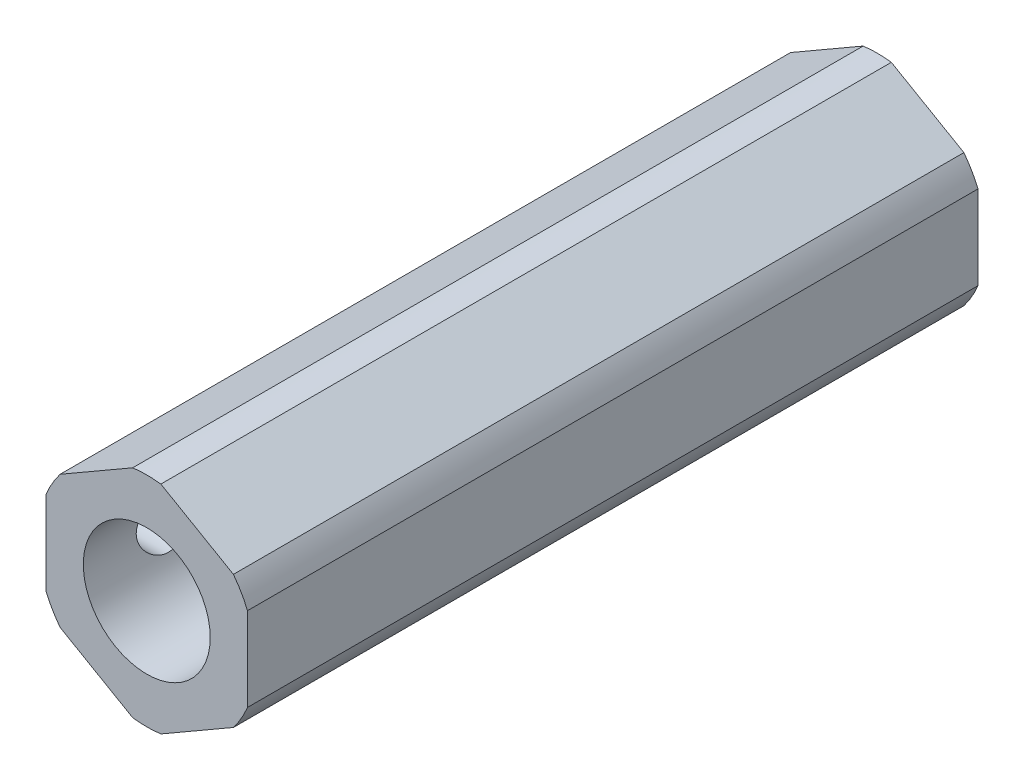
SolidWorks part; units mm, degrees
material "ThunderHex"
ref_plane "Front Plane" through (0, 0, 0) normal (0, 0, 1) x (1, 0, 0)
ref_plane "Top Plane" through (0, 0, 0) normal (0, 1, 0) x (1, 0, 0)
ref_plane "Right Plane" through (0, 0, 0) normal (1, 0, 0) x (0, 0, -1)
ref_plane "End1" through (0, 0, 23.0188) normal (0, 0, 1) x (1, 0, 0)
ref_plane "End2" through (0, 0, -23.0188) normal (0, 0, 1) x (1, 0, 0)
sketch "Sketch1" plane through (0, 0, 0) normal (0, 0, 1) x (1, 0, 0)
  circle A0 centre (0, 0) radius 6.35
  dimension "D1" = 12.7
extrude "Basic Rod" add sketch "Sketch1" along normal up to surface (23.0188 mm away) and the other way up to surface (23.0188 mm away) up to plane "End1" other way up to plane "End2"
ref_axis "Center Axis" through (0, 0, -19.2087) along (0, 0, 1)
sketch "Sketch8" plane through (0, 0, 0) normal (0, 0, 1) x (1, 0, 0)
  line L0 (-5.4616, 4.1791) -> (-6.35, 3.6662) construction
  line L1 (-0.8884, 6.8194) -> (-5.4616, 4.1791)
  line L2 (-6.35, 2.6403) -> (-6.35, -2.6403)
  line L3 (-5.4616, -4.1791) -> (-0.8884, -6.8194)
  line L4 (0.8884, -6.8194) -> (5.4616, -4.1791)
  line L5 (6.35, -2.6403) -> (6.35, 2.6403)
  line L6 (5.4616, 4.1791) -> (0.8884, 6.8194)
  line L7 (-6.35, 3.6662) -> (-6.35, 2.6403) construction
  line L8 (0, 7.3323) -> (-0.8884, 6.8194) construction
  line L9 (0.8884, 6.8194) -> (0, 7.3323) construction
  line L10 (6.35, 3.6662) -> (5.4616, 4.1791) construction
  line L11 (6.35, 2.6403) -> (6.35, 3.6662) construction
  line L12 (6.35, -3.6662) -> (6.35, -2.6403) construction
  line L13 (5.4616, -4.1791) -> (6.35, -3.6662) construction
  line L14 (0, -7.3323) -> (0.8884, -6.8194) construction
  line L15 (-0.8884, -6.8194) -> (0, -7.3323) construction
  line L16 (-6.35, -3.6662) -> (-5.4616, -4.1791) construction
  line L17 (-6.35, -2.6403) -> (-6.35, -3.6662) construction
  circle A0 centre (0, 0) radius 6.35 construction
  arc A1 (-6.35, -2.6403) -> (-5.4616, -4.1791) centre (0, 0) ccw
  circle A2 centre (0, 0) radius 6.35 construction
  arc A3 (-6.35, 2.6403) -> (-6.35, -2.6403) centre (0, 0) ccw construction
  arc A4 (-0.8884, 6.8194) -> (-5.4616, 4.1791) centre (0, 0) ccw construction
  arc A5 (-5.4616, 4.1791) -> (-6.35, 2.6403) centre (0, 0) ccw
  arc A6 (5.4616, 4.1791) -> (0.8884, 6.8194) centre (0, 0) ccw construction
  arc A7 (0.8884, 6.8194) -> (-0.8884, 6.8194) centre (0, 0) ccw
  arc A8 (6.35, -2.6403) -> (6.35, 2.6403) centre (0, 0) ccw construction
  arc A9 (6.35, 2.6403) -> (5.4616, 4.1791) centre (0, 0) ccw
  arc A10 (0.8884, -6.8194) -> (5.4616, -4.1791) centre (0, 0) ccw construction
  arc A11 (5.4616, -4.1791) -> (6.35, -2.6403) centre (0, 0) ccw
  arc A12 (-5.4616, -4.1791) -> (-0.8884, -6.8194) centre (0, 0) ccw construction
  arc A13 (-0.8884, -6.8194) -> (0.8884, -6.8194) centre (0, 0) ccw
  dimension "D1" = 13.7541
extrude "THex" add sketch "Sketch8" along normal mid plane 46.0375
sketch "Sketch5" plane through (0, 0, 0) normal (0, 0, 1) x (1, 0, 0)
  line L1 (-3.6662, 6.35) -> (-7.3323, 0)
  line L2 (-7.3323, 0) -> (-3.6662, -6.35)
  line L3 (-3.6662, -6.35) -> (3.6662, -6.35)
  line L4 (3.6662, -6.35) -> (7.3323, 0)
  line L5 (7.3323, 0) -> (3.6662, 6.35)
  line L6 (3.6662, 6.35) -> (-3.6662, 6.35)
  circle A0 centre (0, 0) radius 6.35 construction
  circle A2 centre (0, 0) radius 6.35 construction
extrude "Hex" [suppressed] add sketch "Sketch5" along normal mid plane 46.0375
sketch "Sketch7" plane through (0, 0, 0) normal (1, 0, 0) x (0, 0, -1)
  line L0 (0, 0) -> (-50000, 0) construction
  line L1 (-23.0188, 5.9436) -> (-24.0348, 5.9436)
  line L2 (-24.0348, 5.9436) -> (-24.0348, 6.35)
  line L3 (-24.0348, 6.35) -> (-25.0508, 6.35)
  line L4 (-25.5588, 5.842) -> (-25.5588, 0)
  line L5 (-25.5588, 0) -> (-23.0188, 0)
  line L6 (-23.0188, 0) -> (-23.0188, 5.9436)
  line L7 (-25.0508, 6.35) -> (-25.5588, 5.842)
  line L8 (19.2087, 0) -> (-19.2087, 0) construction
  line L9 (-23.0188, 5.2388) -> (-23.0188, -5.2388) construction
  point P7 (-25.5588, 6.35)
  dimension "D1" = 12.7
  dimension "D4" = 1.016
  dimension "D2" = 0.4064
  dimension "D3" = 2.54
revolve "1stSnapRing" [suppressed] add sketch "Sketch7" angle 360 about axis through (0, 0, -19.2087) along (0, 0, 1)
mirror "2ndSnapRing" [suppressed] about plane through (0, 0, 0) normal (0, 0, 1)
sketch "Sketch2" plane through (0, 0, 0) normal (0, 0, 1) x (1, 0, 0)
  circle A0 centre (0, 0) radius 2.1158
  dimension "D1" = 4.2316
extrude "Internal Cut" cut sketch "Sketch2" against normal through all both and the other way through all
sketch "Sketch9" plane through (0, 0, 23.0188) normal (0, 0, 1) x (1, 0, 0)
  circle A0 centre (0, 0) radius 4
  dimension "D1" = 8
extrude "Cut-Extrude1" cut sketch "Sketch9" against normal blind 20
sketch "Sketch10" plane through (-6.35, 0, 0) normal (-1, 0, 0) x (0, 0, 1)
  line L0 (23.0188, 0) -> (18.0175, 0) construction
  line L1 (23.0188, 2.6403) -> (23.0188, -2.6403) construction
  line L2 (18.0175, 0) -> (10.0165, 0) construction
  circle A0 centre (10.0165, 0) radius 1.6662
  circle A1 centre (18.0175, 0) radius 1.6662
  dimension "D1" = 3.3325
  dimension "D2" = 5.0013
  dimension "D3" = 8.001
extrude "Cut-Extrude2" cut sketch "Sketch10" against normal up to next
equation "\"Unit Measure\"= \"Length\"'in"
equation "\"D1@Sketch1\"=\"OD\""
equation "\"D1\"= \"Length\""
equation "\"D1@Sketch2\"=\"ID\""
equation "\"Internal Cut\"= IIF ( \"ID\" = 0 ,  suppressed  ,  unsuppressed  ) "
equation "\"D1@Hex\" = \"Length\""
equation "\"Hex\" = IIF ( \"SelectionType\" = 1 , \"suppressed\" , iif ( \"SelectionType\" = 2 , \"suppressed\" , \"unsuppressed\" ) )"
equation "\"OutsideDiameter\"= \"OD\"'in"
equation "\"ThunderHexDia\"= iif ( \"OD\" < .36 , \"OD\" * 1.1 , iif ( \"OD\" < .40 , .4035 , iif ( \"OD\" < .52 , .5415 , \"OD\" * 1.1 ) ) )"
equation "\"D1@Sketch7\"=\"Thickness\""
equation "\"SRDia\"= iif ( \"OD\" = .5 , ( \"OD\" - .468 ) / 2 , iif ( \"OD\" = .375 , ( \"OD\" - .352 ) / 2 , .050 ) )"
equation "\"D2@Sketch7\"= \"SnapRingDepth\""
equation "\"1stSnapRing\"= iif ( \"SnapRingCount\" > 0 , \"unsuppressed\" , \"suppressed\" )"
equation "\"2ndSnapRing\"= iif ( \"SnapRingCount\" = 2 , \"unsuppressed\" , \"suppressed\" )"
equation "\"D1@End1\" = \"Length\" / 2"
equation "\"D1@End2\" = \"Length\""
equation "\"D1@Sketch8\"=\"ThunderHexDia\""
equation "\"D1@THex\" = \"Length\""
equation "\"THex\"= IIF ( \"SelectionType\" = 0 ,  suppressed  , iif ( \"SelectionType\" = 2 ,  suppressed  ,  unsuppressed  )  ) "
